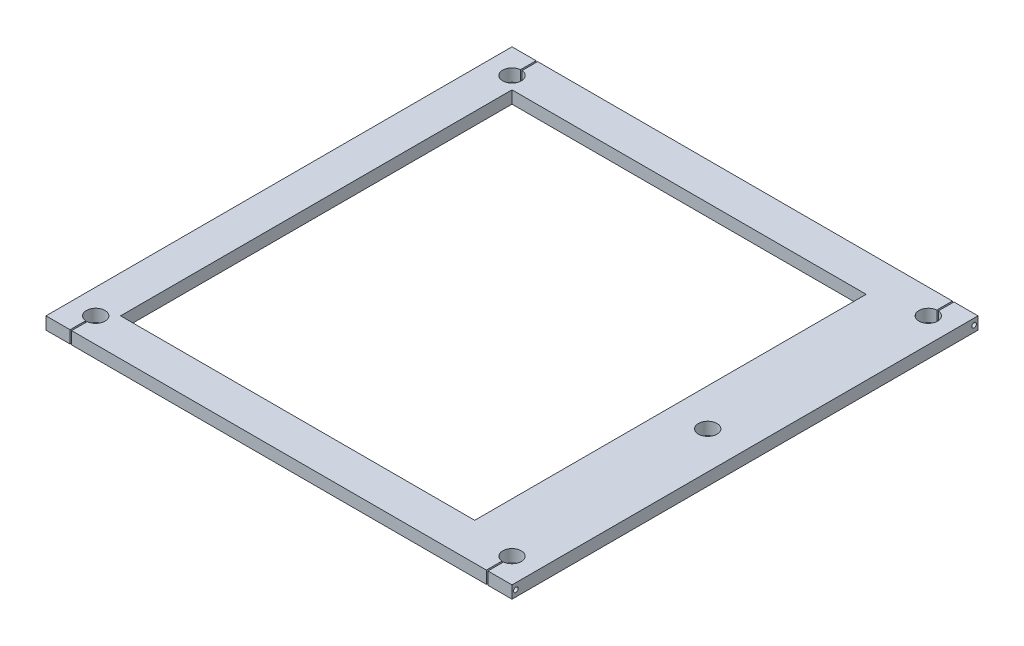
SolidWorks part; units mm, degrees
ref_plane "Front Plane" through (0, 0, 0) normal (0, 0, 1) x (1, 0, 0)
ref_plane "Top Plane" through (0, 0, 0) normal (0, 1, 0) x (1, 0, 0)
ref_plane "Right Plane" through (0, 0, 0) normal (1, 0, 0) x (0, 0, -1)
sketch "Sketch1" plane through (0, 0, 0) normal (0, 1, 0) x (1, 0, 0)
  line L0 (150, 150) -> (150, -150)
  line L1 (-150, -150) -> (150, -150)
  line L2 (-150, -150) -> (-150, 150)
  line L3 (-150, 150) -> (150, 150)
  line L4 (-12, 126) -> (-12, 150) construction
  line L5 (-150, -150) -> (150, 150) construction
  line L6 (-150, 150) -> (150, -150) construction
  line L7 (-126, -126) -> (102, -126)
  line L8 (-126, -126) -> (-126, 126)
  line L9 (-126, 126) -> (102, 126)
  line L10 (102, -126) -> (102, 126)
  line L11 (-126, -126) -> (102, 126) construction
  line L12 (-126, 126) -> (102, -126) construction
  line L14 (-126, 0) -> (-150, 0) construction
  line L15 (-12, -126) -> (-12, -150) construction
  point P0 (-12, 0)
  point P13 (0, 0)
  dimension "D4" = 300
  dimension "D1" = 300
  dimension "D2" = 228
  dimension "D3" = 252
extrude "Boss-Extrude1" add sketch "Sketch1" along normal blind 8
sketch "Sketch2" plane through (0, 0, 0) normal (0, 1, 0) x (1, 0, 0)
  line L0 (150, 150) -> (-150, 150) construction
  line L1 (150, 150) -> (-150, 150) construction
  line L2 (150, -150) -> (150, 150) construction
  line L3 (133.5, 150) -> (134.5, 150)
  line L4 (133.5, 150) -> (133.5, 139.9791)
  line L5 (134, 134) -> (134, 150) construction
  line L6 (134.5, 150) -> (134.5, 139.9791)
  arc A0 (133.5, 139.9791) -> (134.5, 139.9791) centre (134, 134) ccw
  point P6 (131.0158, 128.7948)
  dimension "D1" = 12
  dimension "D2" = 16
  dimension "D3" = 16
  dimension "D4" = 1
extrude "Cut-Extrude1" cut sketch "Sketch2" along normal through all
sketch "Sketch3" plane through (150, 0, 0) normal (1, 0, 0) x (0, 0, -1)
  line L0 (147.5, 4) -> (150, 4) construction
  line L2 (150, 8) -> (150, 0) construction
  circle A0 centre (147.5, 4) radius 1.5
  dimension "D1" = 3
  dimension "D2" = 2.5
extrude "Cut-Extrude2" cut sketch "Sketch3" against normal up to surface (16.5 mm away) up to face at (133.5, 4, -144.9896)
mirror "Mirror3" about plane through (0, 0, 0) normal (0, 0, 1) of "Cut-Extrude2", "Cut-Extrude1"
sketch "Sketch4" plane through (0, 0, 0) normal (0, 1, 0) x (1, 0, 0)
  line L0 (102, 0) -> (150, 0) construction
  line L1 (102, -126) -> (102, 126) construction
  line L2 (150, -150) -> (150, 150) construction
  circle A0 centre (126, 0) radius 6
  dimension "D1" = 12
extrude "Cut-Extrude4" cut sketch "Sketch4" along normal through all
mirror "Mirror4" about plane through (0, 0, 0) normal (1, 0, 0) of "Mirror3", "Cut-Extrude2", "Cut-Extrude1"
